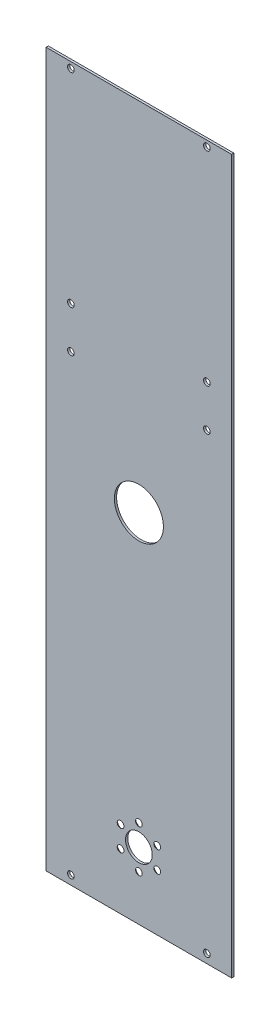
SolidWorks part; units mm, degrees
material "6061 Сплав"
ref_plane "Front Plane" through (0, 0, 0) normal (0, 0, 1) x (1, 0, 0)
ref_plane "Top Plane" through (0, 0, 0) normal (0, 1, 0) x (1, 0, 0)
ref_plane "Right Plane" through (0, 0, 0) normal (1, 0, 0) x (0, 0, -1)
sketch "Sketch1" plane through (0, 0, 0) normal (0, 0, 1) x (1, 0, 0)
  line L1 (41.6, -160) -> (-41.6, -160)
  line L2 (41.6, -160) -> (41.6, 160)
  line L3 (41.6, 160) -> (-41.6, 160)
  line L4 (-41.6, -160) -> (-41.6, 160)
  line L5 (41.6, -160) -> (-41.6, 160) construction
  line L6 (41.6, 160) -> (-41.6, -160) construction
  point P0 (0, 0)
  dimension "D1" = 83.2
  dimension "D2" = 320
extrude "Boss-Extrude1" add sketch "Sketch1" along normal blind 1
hole_wizard "Ø3.0 (3) Diameter Hole1" positions "Sketch3" profile "Sketch2" hole size "Ø3.0" standard "ANSI Metric"
sketch "Sketch3" plane through (0, 0, 1) normal (0, 0, 1) x (1, 0, 0)
  line L6 (-41.6, -160) -> (41.6, -160) construction
  line L9 (41.6, 160) -> (-41.6, 160) construction
  line L10 (0, 160) -> (0, 163.7587) construction
  line L11 (0, 160) -> (0, -152.1509) construction
  point P0 (-30.5, 66)
  point P2 (30.5, 66)
  point P15 (30.5, -156)
  point P17 (-30.5, -156)
  point P54 (-30.5, 157.3)
  point P56 (30.5, 157.3)
  point P58 (-30.5, 47.3)
  point P60 (30.5, 47.3)
  dimension "D2" = 4
  dimension "D3" = 2.7
  dimension "D4" = 4
  dimension "D5" = 30.5
  dimension "D6" = 30.5
  dimension "D7" = 94
  dimension "D8" = 30.5
  dimension "D9" = 2.7
  dimension "D10" = 94
  dimension "D11" = 30.5
  dimension "D12" = 30.5
  dimension "D13" = 30.5
  dimension "D14" = 30.5
  dimension "D15" = 30.5
  dimension "D16" = 112.7
  dimension "D17" = 112.7
sketch "Sketch2" plane through (-30.5, 66, 1) normal (1, 0, 0) x (0, -1, 0)
  line L0 (0, 0) -> (0, 1)
  line L1 (0, 1) -> (1.5, 1)
  line L2 (1.5, 1) -> (1.5, 0)
  line L5 (1.5, 0) -> (0, 0)
  line L10 (0, 1) -> (-1.5, 1) construction
  line L11 (0, -6.35) -> (0, 107.95) construction
  dimension "Hole Dia." = 3
  dimension "Hole Depth" = 1
  dimension "Drill Angle" = 180
sketch "Эскиз1" plane through (0, 0, 1) normal (0, 0, 1) x (1, 0, 0)
  circle A0 centre (0, 0) radius 11
extrude "Вырез-Вытянуть1" cut sketch "Эскиз1" against normal through all
sketch "Эскиз2" plane through (0, 0, 1) normal (0, 0, 1) x (1, 0, 0)
  line L0 (-41.6, -160) -> (41.6, -160) construction
  circle A0 centre (0, -130) radius 6
  dimension "D1" = 12
  dimension "D2" = 30
extrude "Вырез-Вытянуть2" cut sketch "Эскиз2" against normal blind 10
sketch "Эскиз3" plane through (0, 0, 1) normal (0, 0, 1) x (1, 0, 0)
  circle A0 centre (0, -130) radius 6 construction
  circle A1 centre (0, -130) radius 6 construction
  circle A2 centre (0, -120.5) radius 1.5
  dimension "D1" = 3
  dimension "D2" = 9.5
extrude "Вырез-Вытянуть3" cut sketch "Эскиз3" against normal blind 10
chamfer "Фаска1" distance 1 angle 45 1 edges at (1.5, -120.5, 0)
pattern_circular "Круговой массив1" count 6 over 360 about axis through (0, -130, -9) along (0, 0, 1) of "Вырез-Вытянуть3", "Фаска1"
